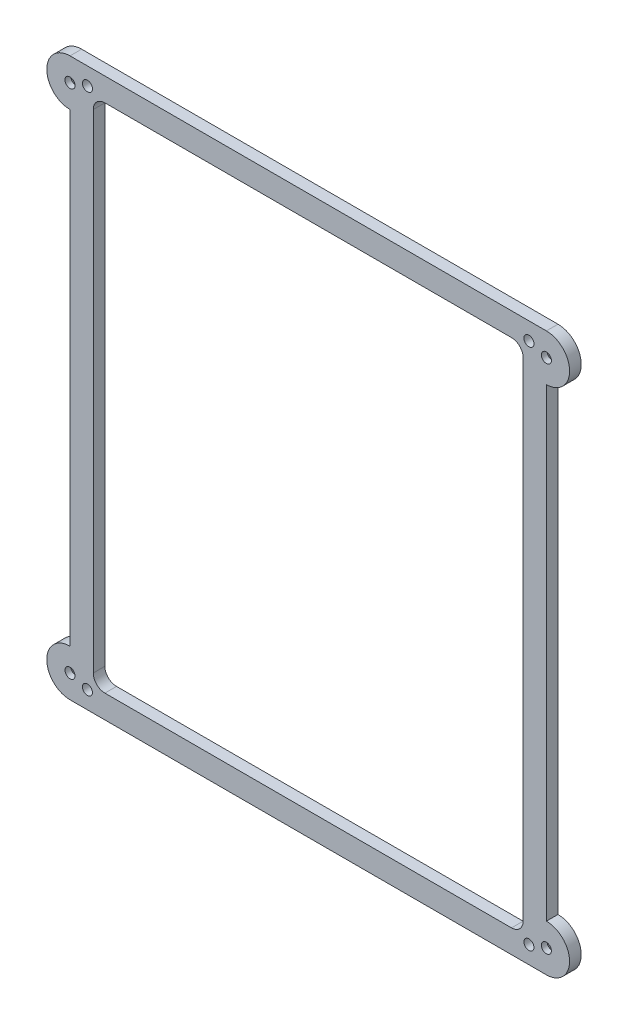
SolidWorks part; units mm, degrees
ref_plane "Front Plane" through (0, 0, 0) normal (0, 0, 1) x (1, 0, 0)
ref_plane "Top Plane" through (0, 0, 0) normal (0, 1, 0) x (1, 0, 0)
ref_plane "Right Plane" through (0, 0, 0) normal (1, 0, 0) x (0, 0, -1)
sketch "Sketch1" plane through (0, 0, 0) normal (0, 0, 1) x (1, 0, 0)
  line L0 (254, 6.35) -> (254, -273.05) construction
  line L1 (-19.05, -285.75) -> (241.3, -285.75)
  line L2 (-19.05, -285.75) -> (-19.05, 19.05)
  line L3 (-19.05, 19.05) -> (241.3, 19.05)
  line L4 (241.3, -285.75) -> (241.3, 19.05)
  line L5 (-19.05, -285.75) -> (241.3, 19.05) construction
  line L6 (-19.05, 19.05) -> (241.3, -285.75) construction
  line L7 (-6.35, 6.35) -> (228.6, 6.35)
  line L8 (-6.35, 6.35) -> (-6.35, -273.05)
  line L9 (-6.35, -273.05) -> (228.6, -273.05)
  line L10 (228.6, 6.35) -> (228.6, -273.05)
  line L11 (-6.35, 6.35) -> (228.6, -273.05) construction
  line L12 (-6.35, -273.05) -> (228.6, 6.35) construction
  circle A0 centre (-9.525, -276.225) radius 2.75
  circle A1 centre (231.775, -276.225) radius 2.75
  circle A2 centre (231.775, 9.525) radius 2.75
  circle A3 centre (-9.525, 9.525) radius 2.75
  circle A4 centre (231.775, 9.525) radius 2.75 construction
  arc A5 (241.3, 19.05) -> (241.3, -6.35) centre (241.3, 6.35) cw
  arc A6 (241.3, -260.35) -> (241.3, -285.75) centre (241.3, -273.05) cw
  arc A7 (-19.05, 19.05) -> (-19.05, -6.35) centre (-19.05, 6.35) ccw
  arc A8 (-19.05, -285.75) -> (-19.05, -260.35) centre (-19.05, -273.05) cw
  circle A9 centre (-19.05, -273.05) radius 2.75
  circle A10 centre (241.3, -273.05) radius 2.75
  circle A11 centre (241.3, 6.35) radius 2.75
  circle A12 centre (-19.05, 6.35) radius 2.75
  point P4 (111.125, -133.35)
  point P24 (111.125, -133.35)
  dimension "D1" = 12.7
  dimension "D2" = 12.7
  dimension "D3" = 12.7
extrude "Boss-Extrude1" add sketch "Sketch1" along normal blind 6.35 contours L1 L4 L3 L2 A3 A2 A1 A0 L7 L10 L9 L8 | A6 L4 | A5 L4 | A9 L2 A8 | A12 L2 A7 region at (-15.0414, -280.775, 0) region at (-24.6478, -273.05, 0) region at (246.8978, -273.05, 0) region at (-24.6478, 6.35, 0) region at (246.8978, 6.35, 0)
fillet "Fillet1" radius 6.35 4 edges at (-6.35, -273.05, 3.175) (-6.35, 6.35, 3.175) (228.6, 6.35, 3.175) (228.6, -273.05, 3.175)
chamfer "Chamfer1" distance 3.175 angle 45 4 edges at (-16.3, 6.35, 0) (244.05, 6.35, 0) (244.05, -273.05, 0) (-16.3, -273.05, 0)
